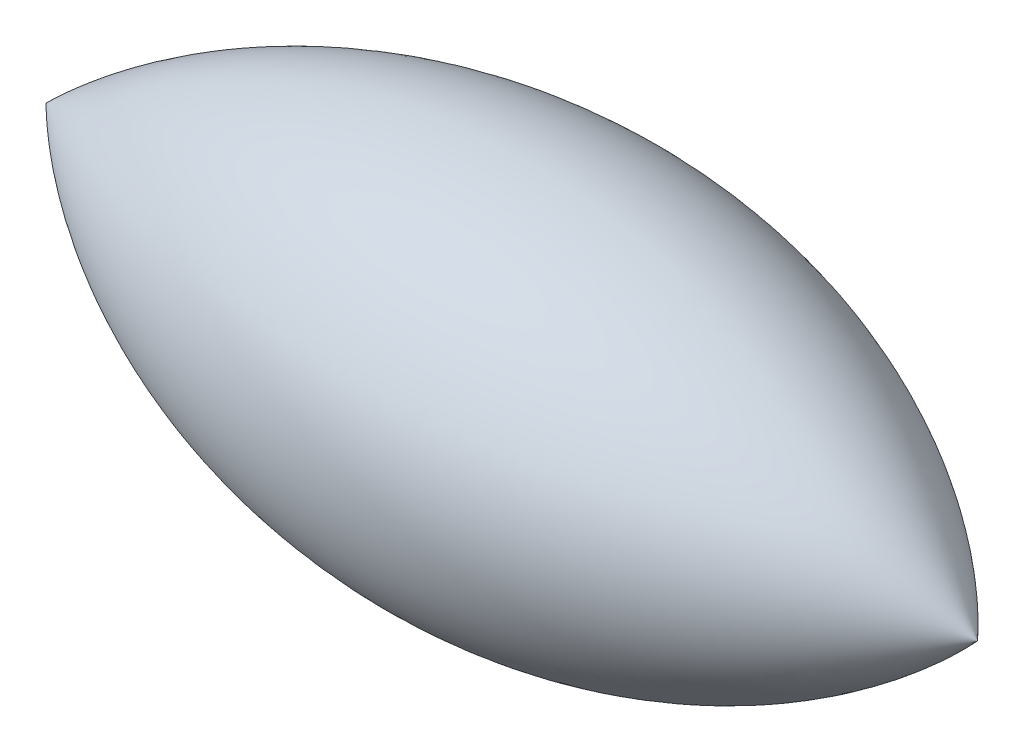
SolidWorks part; units mm, degrees
ref_plane "Front" through (0, 0, 0) normal (0, 0, 1) x (1, 0, 0)
ref_plane "Top" through (0, 0, 0) normal (0, 1, 0) x (1, 0, 0)
ref_plane "Right" through (0, 0, 0) normal (1, 0, 0) x (0, 0, -1)
sketch "Sketch1" plane through (0, 0, 0) normal (0, 0, 1) x (1, 0, 0)
  line L0 (-417.5311, 136.3039) -> (375.8174, 136.3039) construction
  line L1 (-417.5311, 136.3039) -> (375.8174, 136.3039)
  spline S0 degree 3 poles (-417.5311, 136.3039) (-206.5847, 344.4181) (168.1363, 360.2847) (375.8174, 136.3039) knots 0 0 0 0 1 1 1 1
revolve "Revolve1" add sketch "Sketch1" angle 360 about L0
